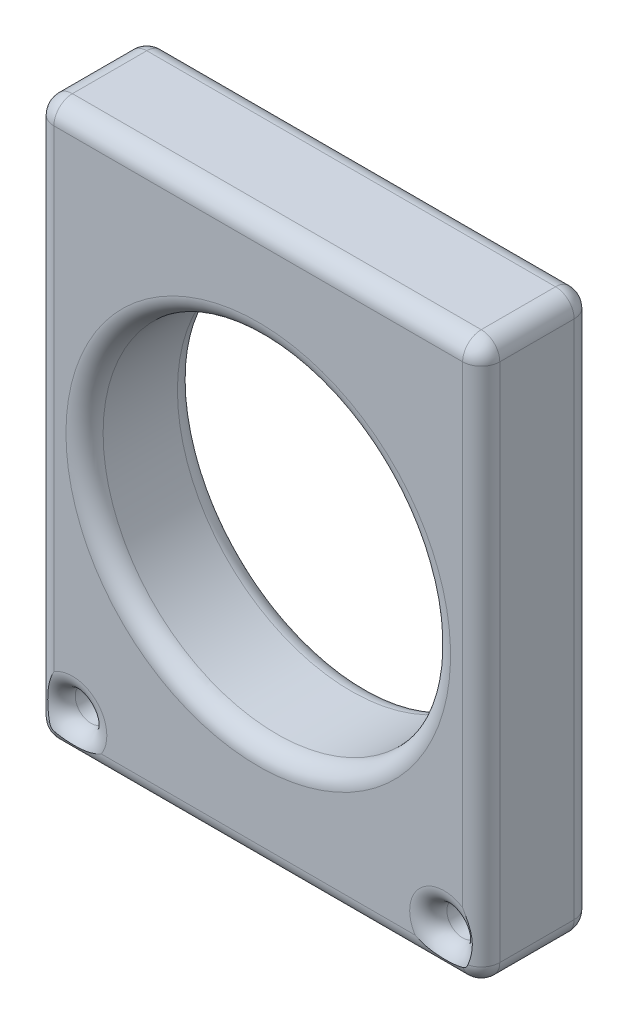
SolidWorks part; units mm, degrees
ref_plane "前视基准面" through (0, 0, 0) normal (0, 0, 1) x (1, 0, 0)
ref_plane "上视基准面" through (0, 0, 0) normal (0, 1, 0) x (1, 0, 0)
ref_plane "右视基准面" through (0, 0, 0) normal (1, 0, 0) x (0, 0, -1)
other "Configuration Table"
sketch "草图1" plane through (0, 0, 0) normal (0, 0, 1) x (1, 0, 0)
  line L1 (-24, -24) -> (24, -24)
  line L2 (-24, -24) -> (-24, 36)
  line L3 (-24, 36) -> (24, 36)
  line L4 (24, -24) -> (24, 36)
  line L5 (-24, -24) -> (24, 36) construction
  line L6 (-24, 36) -> (24, -24) construction
  circle A0 centre (0, 6) radius 18.7
  circle A1 centre (20, -20) radius 1.7
  circle A2 centre (-20, -20) radius 1.7
  point P0 (0, 6)
extrude "凸台-拉伸1" add sketch "草图1" along normal mid plane 12
fillet "圆角1" radius 2 18 edges at (-18.3, -20, -6) (-18.3, -20, 6) (21.7, -20, -6) (21.7, -20, 6) (18.7, 6, -6) (18.7, 6, 6) (24, 6, -6) (0, 36, -6) (-24, 6, -6) (0, -24, -6) (24, 6, 6) (0, 36, 6) (-24, 6, 6) (0, -24, 6) (24, -24, 0) (-24, -24, 0) (-24, 36, 0) (24, 36, 0) tangent propagation no
